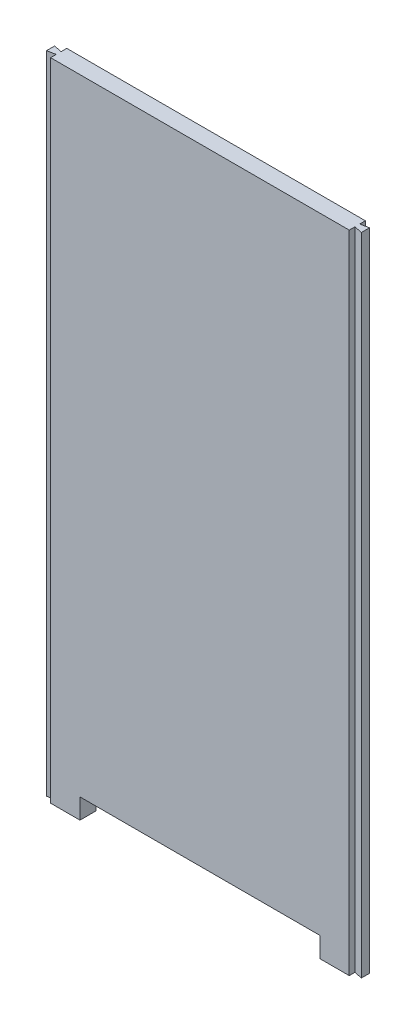
SolidWorks part; units mm, degrees
ref_plane "Front Plane" through (0, 0, 0) normal (0, 0, 1) x (1, 0, 0)
ref_plane "Top Plane" through (0, 0, 0) normal (0, 1, 0) x (1, 0, 0)
ref_plane "Right Plane" through (0, 0, 0) normal (1, 0, 0) x (0, 0, -1)
sketch "Sketch1" plane through (0, 0, 0) normal (0, 0, 1) x (1, 0, 0)
  line L1 (0, 0) -> (37, 0)
  line L2 (0, 0) -> (0, 80)
  line L3 (0, 80) -> (37, 80)
  line L4 (37, 0) -> (37, 80)
  dimension "D1" = 80
  dimension "D2" = 37
extrude "Boss-Extrude1" add sketch "Sketch1" along normal blind 2
sketch "Sketch2" plane through (0, 80, 0) normal (0, 1, 0) x (1, 0, 0)
  line L0 (38.0071, -1) -> (37, -1) construction
  line L3 (38.0071, -1.5) -> (37, -1.5) construction
  line L5 (38.0071, -0.5) -> (37, -0.7)
  line L7 (37, -1.3) -> (37, -0.7)
  line L9 (18.5, 0) -> (18.5, -2) construction
  line L10 (37, 0) -> (0, 0) construction
  line L11 (37, -2) -> (0, -2) construction
  line L16 (-1.0071, -1.5) -> (0, -1.5) construction
  line L17 (0, -1.5) -> (0, -1.3)
  line L18 (-1.0071, -1.5) -> (0, -1.3)
  line L19 (-1.0071, -1.5) -> (-1.0071, -0.5)
  line L20 (-1.0071, -1) -> (0, -1) construction
  line L21 (0, -1.3) -> (0, -0.7)
  line L22 (-1.0071, -0.5) -> (0, -0.7)
  line L23 (38.0071, -1.5) -> (38.0071, -0.5)
  line L24 (38.0071, -1.5) -> (37, -1.3)
  line L25 (37, -1.5) -> (37, -1.3)
  line M3 (0, 0) -> (0, -2)
  line M5 (37, -2) -> (37, 0)
extrude "Boss-Extrude2" add sketch "Sketch2" against normal up to surface (80 mm away) contours L22 L19 L18 M3 | L24 L23 L5 M5 up to face at (18.5, 0, 1)
sketch "Sketch3" plane through (0, 0, 2) normal (0, 0, 1) x (1, 0, 0)
  line L0 (0, 0) -> (18.5, 0) construction
  line L1 (0, 0) -> (37, 0) construction
  line L2 (18.5, 0) -> (18.5, 2.5) construction
  line L3 (3.6365, 2.5) -> (33.3635, 2.5)
  line L4 (33.3635, 2.5) -> (33.3635, 0)
  line L5 (3.6365, 2.5) -> (3.6365, 0)
  line L6 (3.6365, 0) -> (33.3635, 0)
  dimension "D1" = 2.5
extrude "Cut-Extrude1" cut sketch "Sketch3" against normal up to surface (2 mm away) contours L3 L4 L6 L5 up to face at (18.5, 40, 0)
